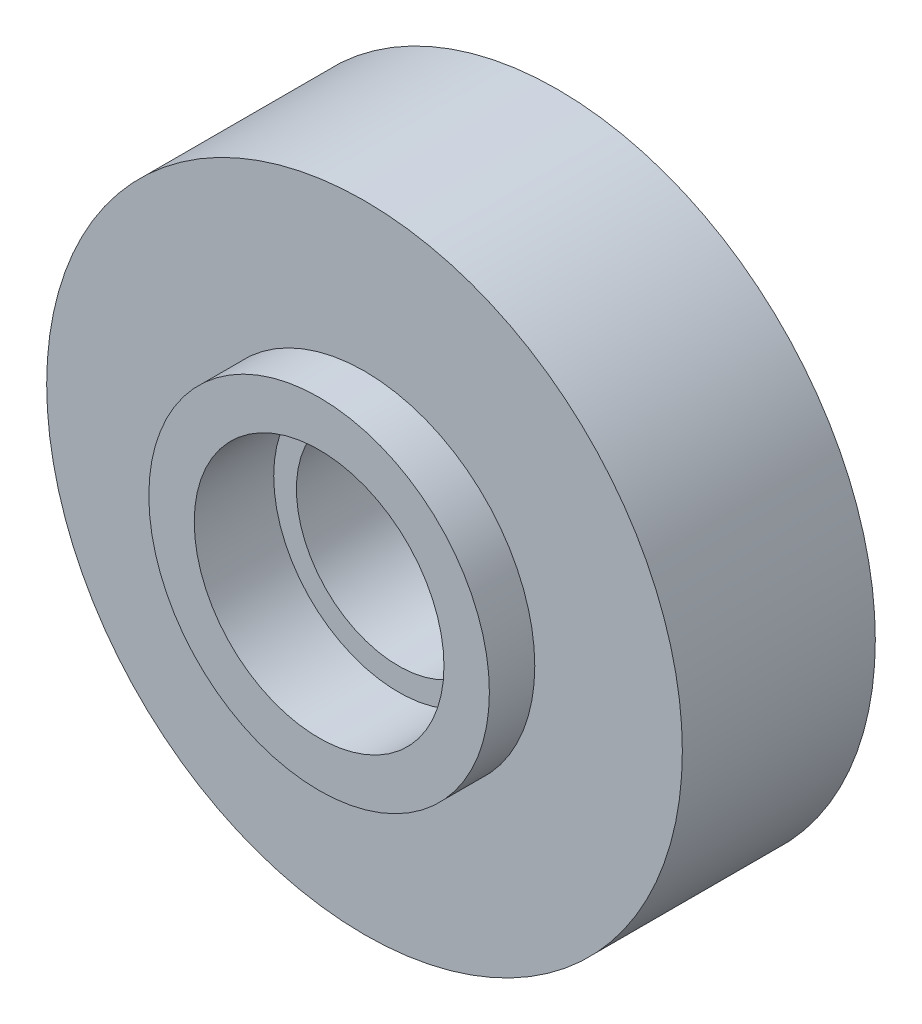
SolidWorks part; units mm, degrees
material "Polybutadiene (PB)"
ref_plane "Front Plane" through (0, 0, 0) normal (0, 0, 1) x (1, 0, 0)
ref_plane "Top Plane" through (0, 0, 0) normal (0, 1, 0) x (1, 0, 0)
ref_plane "Right Plane" through (0, 0, 0) normal (1, 0, 0) x (0, 0, -1)
sketch "Sketch1" plane through (0, 0, 0) normal (0, 0, 1) x (1, 0, 0)
  circle A0 centre (0, 0) radius 28
  dimension "D1" = 56
extrude "Boss-Extrude1" add sketch "Sketch1" along normal blind 17
sketch "Sketch2" plane through (0, 0, 17) normal (0, 0, 1) x (1, 0, 0)
  circle A0 centre (0, 0) radius 11
extrude "Cut-Extrude1" cut sketch "Sketch2" against normal blind 3
sketch "Sketch3" plane through (0, 0, 14) normal (0, 0, 1) x (1, 0, 0)
  circle A0 centre (0, 0) radius 9
extrude "Cut-Extrude2" cut sketch "Sketch3" against normal through all
sketch "Sketch4" plane through (0, 0, 0) normal (0, 0, -1) x (-1, 0, 0)
  circle A0 centre (0, 0) radius 11
extrude "Cut-Extrude3" cut sketch "Sketch4" against normal blind 6.5
sketch "Sketch6" plane through (0, 0, 17) normal (0, 0, 1) x (1, 0, 0)
  circle A0 centre (0, 0) radius 15
  circle A1 centre (0, 0) radius 11
extrude "Boss-Extrude2" add sketch "Sketch6" along normal blind 4
